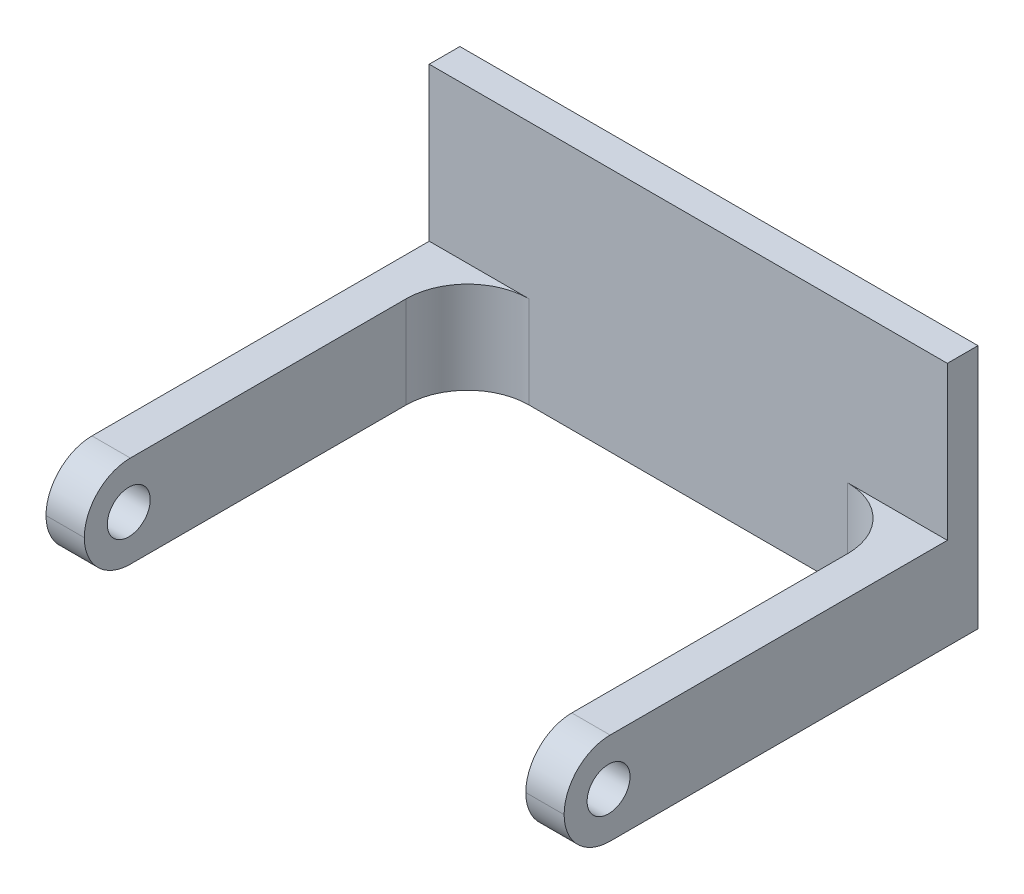
SolidWorks part; units mm, degrees
ref_plane "Front Plane" through (0, 0, 0) normal (0, 0, 1) x (1, 0, 0)
ref_plane "Top Plane" through (0, 0, 0) normal (0, 1, 0) x (1, 0, 0)
ref_plane "Right Plane" through (0, 0, 0) normal (1, 0, 0) x (0, 0, -1)
sketch "Sketch1" plane through (0, 0, 0) normal (0, 0, 1) x (1, 0, 0)
  line L1 (-16.9, -3) -> (16.9, -3)
  line L2 (-16.9, -3) -> (-16.9, 3)
  line L3 (-16.9, 3) -> (16.9, 3)
  line L4 (16.9, -3) -> (16.9, 3)
  line L5 (-16.9, -3) -> (16.9, 3) construction
  line L6 (-16.9, 3) -> (16.9, -3) construction
  point P0 (0, 0)
  dimension "D1" = 33.8
  dimension "D2" = 6
extrude "Boss-Extrude1" add sketch "Sketch1" along normal blind 2
sketch "Sketch2" plane through (0, 0, 2) normal (0, 0, 1) x (1, 0, 0)
  line L0 (-16.9, -3) -> (16.9, -3) construction
  line L1 (-16.9, 3) -> (-14.4, 3)
  line L2 (-16.9, 3) -> (-16.9, -3)
  line L3 (-16.9, -3) -> (-14.4, -3)
  line L4 (-14.4, 3) -> (-14.4, -3)
  line L6 (16.9, 3) -> (14.4, 3)
  line L7 (16.9, 3) -> (16.9, -3)
  line L8 (16.9, -3) -> (14.4, -3)
  line L9 (14.4, 3) -> (14.4, -3)
  dimension "D1" = 2.5
  dimension "D2" = 2.5
extrude "Boss-Extrude2" add sketch "Sketch2" along normal blind 25
sketch "Sketch3" plane through (16.9, 0, 0) normal (1, 0, 0) x (0, 0, -1)
  line L0 (-27, -3) -> (-27, 3) construction
  circle A0 centre (-24.1, 0) radius 1.4
  dimension "D1" = 2.8
  dimension "D2" = 2.9
extrude "Cut-Extrude1" cut sketch "Sketch3" against normal through all
fillet "Fillet1" radius 3 4 edges at (-15.65, -3, 27) (15.65, -3, 27) (-15.65, 3, 27) (15.65, 3, 27)
sketch "Sketch4" plane through (0, 3, 0) normal (0, 1, 0) x (1, 0, 0)
  line L0 (16.9, -24) -> (16.9, 0) construction
  line L1 (-16.9, 0) -> (16.9, 0)
  line L2 (-16.9, 0) -> (-16.9, -2)
  line L3 (-16.9, -2) -> (16.9, -2)
  line L4 (16.9, 0) -> (16.9, -2)
  dimension "D1" = 2
extrude "Boss-Extrude3" add sketch "Sketch4" along normal blind 10
fillet "Fillet2" radius 4 2 edges at (14.4, 0, 2)
